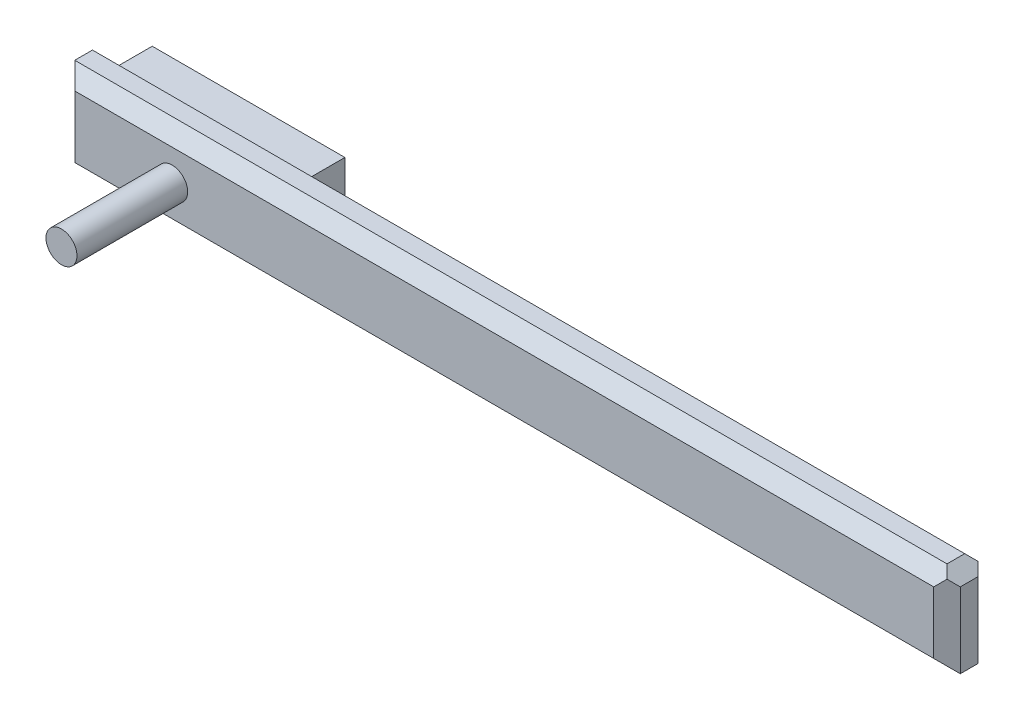
SolidWorks part; units mm, degrees
ref_plane "Front Plane" through (0, 0, 0) normal (0, 0, 1) x (1, 0, 0)
ref_plane "Top Plane" through (0, 0, 0) normal (0, 1, 0) x (1, 0, 0)
ref_plane "Right Plane" through (0, 0, 0) normal (1, 0, 0) x (0, 0, -1)
sketch "Sketch1" plane through (0, 0, 0) normal (0, 0, 1) x (1, 0, 0)
  line L1 (-10, 1) -> (10, 1)
  line L2 (-10, 1) -> (-10, -1)
  line L3 (-10, -1) -> (10, -1)
  line L4 (10, 1) -> (10, -1)
  line L5 (0, -1) -> (0, 1) construction
  line L6 (-10, 0) -> (10, 0) construction
  point P0 (0, 0)
  dimension "D1" = 2
  dimension "D2" = 20
extrude "Boss-Extrude1" add sketch "Sketch1" along normal blind 1
sketch "Sketch2" plane through (0, 0, 1) normal (0, 0, 1) x (1, 0, 0)
  circle A0 centre (-7.5, 0) radius 0.35
  dimension "D2" = 0.7
extrude "Boss-Extrude3" add sketch "Sketch2" along normal blind 2.5
chamfer "Chamfer2" distance 0.3 angle 45 1 edges at (10, 1, 0.5)
chamfer "Chamfer4" distance 0.3 angle 45 5 edges at (10, -0.15, 0) (10, -0.15, 1) (0, -1, 1) (-0.15, 1, 0) (-0.15, 1, 1)
chamfer "Chamfer5" distance 0.3 angle 45 3 edges at (-10, 0, 1) (-10, -0.15, 0) (-0.15, -1, 0)
sketch "Sketch4" plane through (0, 0, 0) normal (0, 0, -1) x (-1, 0, 0)
  line L0 (-9.7, -0.7) -> (9.7, -0.7) construction
  line L1 (9.7, 0.7) -> (5.3489, 0.7)
  line L2 (9.7, 0.7) -> (9.7, -0.7)
  line L3 (9.7, -0.7) -> (5.3489, -0.7)
  line L4 (5.3489, 0.7) -> (5.3489, -0.7)
extrude "Boss-Extrude4" add sketch "Sketch4" along normal blind 0.75
